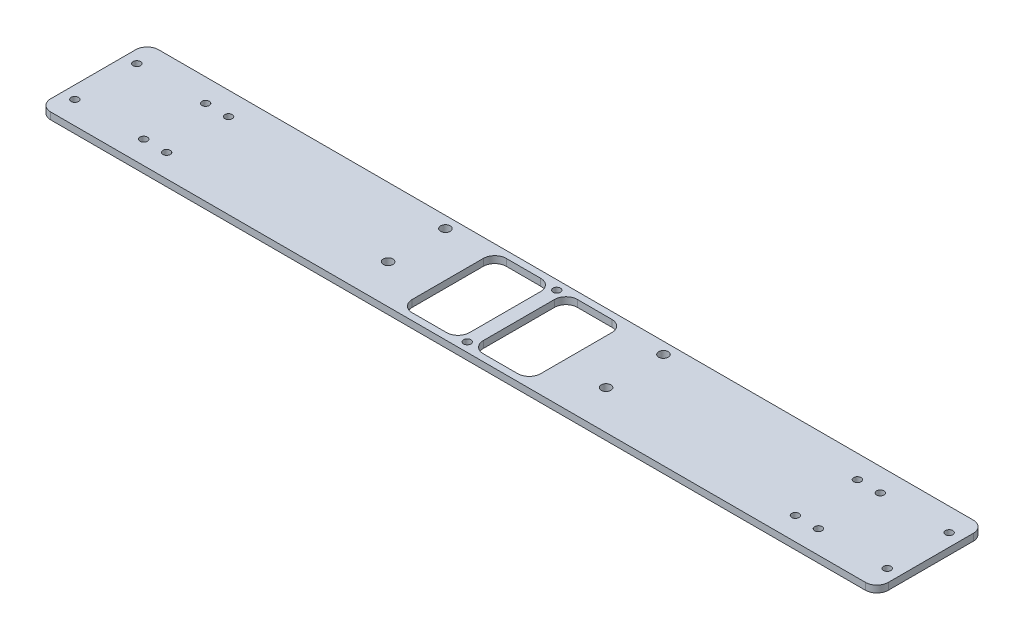
SolidWorks part; units mm, degrees
material "延性铁"
ref_plane "前视基准面" through (0, 0, 0) normal (0, 0, 1) x (1, 0, 0)
ref_plane "上视基准面" through (0, 0, 0) normal (0, 1, 0) x (1, 0, 0)
ref_plane "右视基准面" through (0, 0, 0) normal (1, 0, 0) x (0, 0, -1)
ref_plane "基准面4" through (0, 0, 0) normal (0, -1, 0) x (1, 0, 0)
sketch "草图1" plane through (0, 0, 0) normal (0, -1, 0) x (1, 0, 0)
  line L0 (-228.113, -23.5) -> (-198.113, -23.5) construction
  line L1 (-182.5, -47) -> (182.5, -47)
  line L2 (3, -3) -> (28, -3)
  line L3 (-182.5, 0) -> (182.5, 0)
  line L4 (-182.5, 0) -> (-182.5, -47)
  line L5 (-3, -44) -> (-28, -44)
  line L6 (228.113, -23.5) -> (198.113, -23.5) construction
  line L7 (182.5, 0) -> (182.5, -47)
  line L8 (-3, -44) -> (-3, -3)
  line L9 (-3, -3) -> (-28, -3)
  line L10 (-28, -44) -> (-28, -3)
  line L11 (28, -44) -> (28, -3)
  line L12 (0, 175.9702) -> (0, -175.9702) construction
  line L13 (3, -44) -> (28, -44)
  line L14 (3, -44) -> (3, -3)
  circle A0 centre (-47.5, -17) radius 2.1
  circle A1 centre (-47.5, -42) radius 2.1
  circle A2 centre (-137, -10) radius 1.6
  circle A3 centre (-177, -37) radius 1.6
  circle A4 centre (-137, -37) radius 1.6
  circle A5 centre (177, -10) radius 1.6
  circle A6 centre (137, -37) radius 1.6
  circle A7 centre (177, -37) radius 1.6
  circle A8 centre (137, -10) radius 1.6
  circle A9 centre (47.5, -42) radius 2.1
  circle A10 centre (-177, -10) radius 1.6
  circle A11 centre (47.5, -17) radius 2.1
  circle A12 centre (0, -43) radius 1.6
  circle A13 centre (0, -4) radius 1.6
  circle A14 centre (-147, -10) radius 1.6
  circle A15 centre (-147, -37) radius 1.6
  circle A16 centre (147, -10) radius 1.6
  circle A17 centre (147, -37) radius 1.6
  point P13 (0, -47)
  point P39 (0, 0)
  dimension "D3" = 10
  dimension "D6" = 4
  dimension "D14" = 13.5
  dimension "D15" = 25
  dimension "D16" = 25
  dimension "D1" = 5.5
  dimension "D10" = 47.5
  dimension "D11" = 10
  dimension "D12" = 3
  dimension "D4" = 47.5
  dimension "D5" = 47
  dimension "D2" = 40
  dimension "D7" = 30
  dimension "D8" = 5
  dimension "D9" = 177
  dimension "D13" = 10
  dimension "D18" = 3
  dimension "D19" = 3
extrude "凸台-拉伸1" add sketch "草图1" against normal blind 3
fillet "圆角1" radius 5 12 edges at (182.5, 1.5, -47) (182.5, 1.5, 0) (-182.5, 1.5, -47) (-182.5, 1.5, 0) (-3, 1.5, -3) (-28, 1.5, -3) (-3, 1.5, -44) (-28, 1.5, -44) (28, 1.5, -3) (3, 1.5, -3) (28, 1.5, -44) (3, 1.5, -44) first distance on face at (182.5, 1.5, -23.5) first distance on face at (-182.5, 1.5, -23.5) first distance on face at (-3, 1.5, -23.5) first distance on face at (-15.5, 1.5, -3) first distance on face at (-15.5, 1.5, -44) first distance on face at (-28, 1.5, -23.5) first distance on face at (28, 1.5, -23.5) first distance on face at (15.5, 1.5, -3) first distance on face at (15.5, 1.5, -44) first distance on face at (3, 1.5, -23.5)
